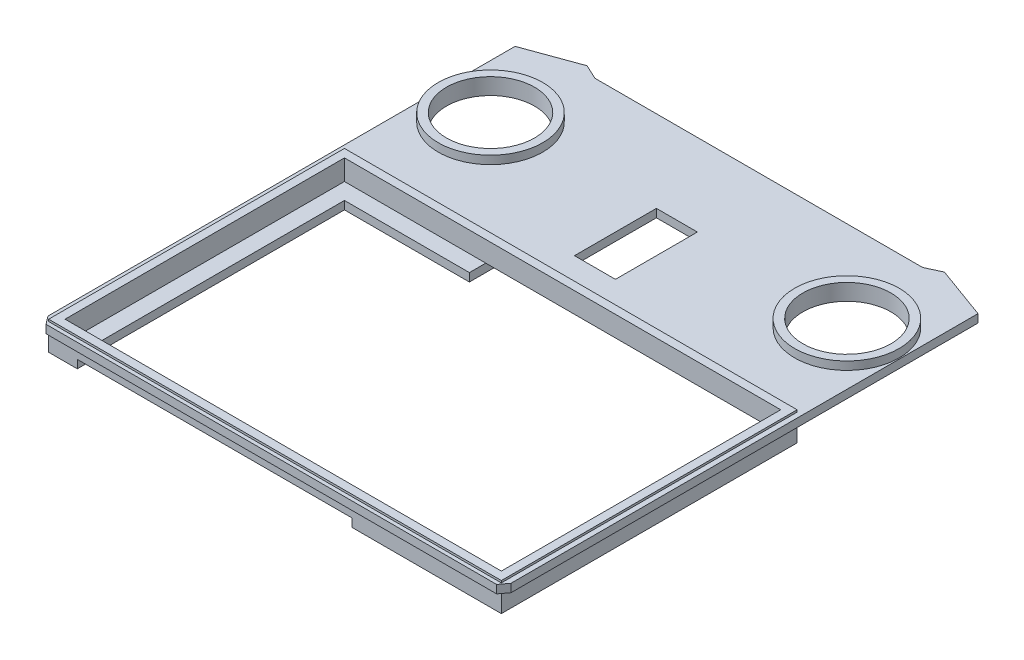
SolidWorks part; units mm, degrees
ref_plane "Front Plane" through (0, 0, 0) normal (0, 0, 1) x (1, 0, 0)
ref_plane "Top Plane" through (0, 0, 0) normal (0, 1, 0) x (1, 0, 0)
ref_plane "Right Plane" through (0, 0, 0) normal (1, 0, 0) x (0, 0, -1)
ref_axis "X Axis" through (-109.587, 0, 0) along (1, 0, 0)
ref_axis "Y Axis" through (0, 0, -140.1599) along (0, 0, 1)
ref_axis "Z Axis" through (0, 50.6832, 0) along (0, -1, 0)
ref_plane "LCD Plane" through (0, 8.5, 0) normal (0, 1, 0) x (1, 0, 0)
sketch "Sketch1" plane through (0, 8.5, 0) normal (0, 1, 0) x (1, 0, 0)
  line L0 (-55.25, 36.1) -> (55.25, 36.1)
  line L1 (-53.25, -34.1) -> (53.25, -34.1)
  line L2 (-53.25, -34.1) -> (-53.25, 34.1)
  line L3 (-53.25, 34.1) -> (53.25, 34.1)
  line L4 (53.25, -34.1) -> (53.25, 34.1)
  line L5 (-53.25, -34.1) -> (53.25, 34.1) construction
  line L6 (-53.25, 34.1) -> (53.25, -34.1) construction
  line L7 (55.25, -36.1) -> (55.25, 36.1)
  line L8 (-55.25, -36.1) -> (55.25, -36.1)
  line L9 (-55.25, -36.1) -> (-55.25, 36.1)
  point P0 (0, 0)
  point P3 (0, 0)
  dimension "D1" = 106.5
  dimension "D2" = 68.2
  dimension "D3" = 2
extrude "Boss-Extrude1" add sketch "Sketch1" along normal blind 5
sketch "Sketch2" plane through (0, 8.5, 0) normal (0, 1, 0) x (1, 0, 0)
  line L0 (-55.25, 36.1) -> (-55.25, -36.1)
  line L1 (-55.25, -36.1) -> (-48.25, -36.1)
  line L2 (55.25, -36.1) -> (55.25, 36.1)
  line L3 (55.25, 36.1) -> (48.25, 36.1)
  line L4 (-53.25, 34.1) -> (-53.25, -34.1) construction
  line L5 (-53.25, -34.1) -> (53.25, -34.1) construction
  line L6 (53.25, -34.1) -> (53.25, 34.1) construction
  line L7 (53.25, 34.1) -> (-53.25, 34.1) construction
  line L8 (-49.25, 30.1) -> (-49.25, -30.1)
  line L10 (49.25, -30.1) -> (49.25, 30.1)
  line L12 (-49.25, -30.1) -> (49.25, -30.1) construction
  line L13 (49.25, 30.1) -> (-49.25, 30.1) construction
  line L14 (-49.25, 30.1) -> (-18.75, 30.1)
  line L15 (-18.75, 30.1) -> (-18.75, 36.1)
  line L16 (49.25, 30.1) -> (48.25, 30.1)
  line L17 (48.25, 30.1) -> (48.25, 36.1)
  line L18 (-18.75, 36.1) -> (-55.25, 36.1)
  line L19 (-49.25, -30.1) -> (-48.25, -30.1)
  line L21 (49.25, -30.1) -> (18.75, -30.1)
  line L23 (-55.25, -36.1) -> (55.25, -36.1) construction
  line L24 (-48.25, -30.1) -> (-48.25, -36.1)
  line L25 (-53.25, -34.1) -> (53.25, -34.1) construction
  line L26 (18.75, -36.1) -> (55.25, -36.1)
  line L27 (-18.75, 30.1) -> (48.25, 30.1) construction
  line L28 (-48.25, -30.1) -> (18.75, -30.1) construction
  line L29 (18.75, -30.1) -> (18.75, -36.1)
  dimension "D1" = 4
  dimension "D2" = 67
  dimension "D3" = 1
extrude "Boss-Extrude2" add sketch "Sketch2" against normal blind 2
ref_plane "Stick Plane" through (0, 13, 0) normal (0, 1, 0) x (1, 0, 0)
sketch "Sketch4" plane through (0, 13, 0) normal (0, 1, 0) x (1, 0, 0)
  line L0 (0, 0) -> (0, 102.87) construction
  line L2 (-43.5, 60) -> (43.5, 60) construction
  circle A0 centre (-43.5, 60) radius 10.75
  circle A1 centre (43.5, 60) radius 10.75
  circle A2 centre (-43.5, 60) radius 12.75
  circle A3 centre (43.5, 60) radius 12.75
  point P4 (0, 60)
  point P6 (0, 0)
  dimension "D3" = 21.5
  dimension "D1" = 60
  dimension "D2" = 87
  dimension "D4" = 2
extrude "Boss-Extrude3" add sketch "Sketch4" along normal blind 2 separate body
sketch "Sketch5" plane through (0, 13, 0) normal (0, 1, 0) x (1, 0, 0)
  line L0 (-56.5, -35) -> (-56.5, 79)
  line L6 (-40, 82) -> (40, 82)
  line L8 (56.5, 79) -> (56.5, -35)
  line L9 (56.5, -35) -> (55, -37)
  line L10 (55, -37) -> (-55, -37)
  line L11 (-55, -37) -> (-56.5, -35)
  line L12 (0, 0) -> (0, -37) construction
  line L13 (0, 0) -> (0, 82) construction
  line L14 (-56.5, 79) -> (56.5, 79) construction
  line L15 (-56.5, -35) -> (56.5, -35) construction
  line L16 (-53.25, 34.1) -> (-53.25, -34.1)
  line L17 (-53.25, -34.1) -> (53.25, -34.1)
  line L18 (53.25, -34.1) -> (53.25, 34.1)
  line L19 (53.25, 34.1) -> (-53.25, 34.1)
  line L21 (-43.6199, 83.688) -> (-40, 82)
  line L22 (40, 82) -> (43.6199, 83.688)
  line L24 (-43.6199, 83.688) -> (-56.5, 79)
  line L25 (43.6199, 83.688) -> (56.5, 79)
  line L27 (-5, 42) -> (5, 42)
  line L28 (-5, 42) -> (-5, 62)
  line L29 (-5, 62) -> (5, 62)
  line L30 (5, 42) -> (5, 62)
  line L31 (-5, 42) -> (5, 62) construction
  line L32 (-5, 62) -> (5, 42) construction
  circle A0 centre (-43.5, 60) radius 10.75
  circle A1 centre (43.5, 60) radius 10.75
  point P22 (0, 55.245)
  point P29 (0, 52)
  dimension "D9" = 155
  dimension "D1" = 37
  dimension "D2" = 82
  dimension "D3" = 113
  dimension "D4" = 113
  dimension "D5" = 2
  dimension "D6" = 3
  dimension "D7" = 110
  dimension "D8" = 80
  dimension "D10" = 20
  dimension "D11" = 10
  dimension "D12" = 20
  dimension "D13" = 52
extrude "Boss-Extrude4" add sketch "Sketch5" against normal blind 2
